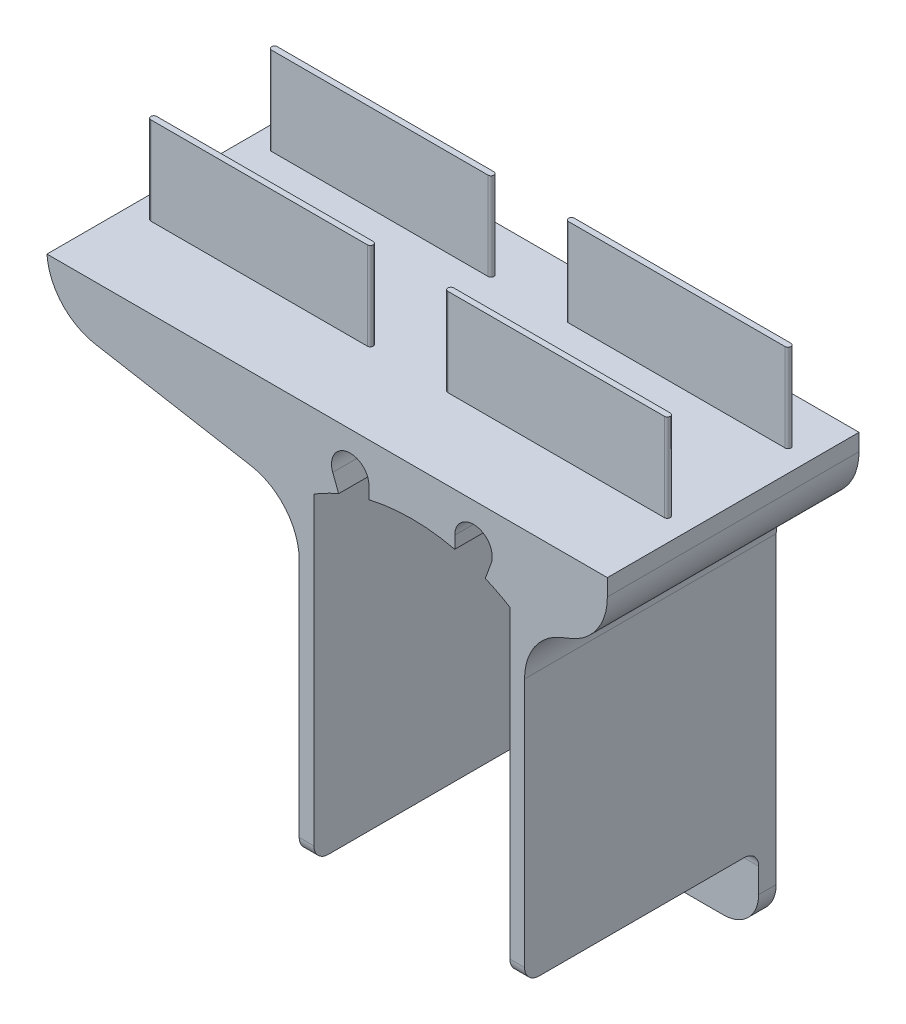
SolidWorks part; units mm, degrees
material "ABS"
ref_plane "Alzado" through (0, 0, 0) normal (0, 0, 1) x (1, 0, 0)
ref_plane "Planta" through (0, 0, 0) normal (0, 1, 0) x (1, 0, 0)
ref_plane "Vista lateral" through (0, 0, 0) normal (1, 0, 0) x (0, 0, -1)
sketch "Croquis4" plane through (0, 0, 0) normal (0, 0, 1) x (1, 0, 0)
  line L0 (-61.9253, -22.5138) -> (-61.9253, 45.4862)
  line L2 (-97.4253, -15.5138) -> (-97.4253, 38.4862) construction
  line L10 (-119.4893, 11.4862) -> (-75.3613, 11.4862) construction
  line L13 (-100.4253, -22.5138) -> (-100.4253, 45.4862)
  line L14 (-81.1753, 11.4862) -> (-81.1753, 55.3392) construction
  line L15 (-94.4253, 51.4862) -> (-67.9253, 51.4862)
  line L18 (-94.4253, -28.5138) -> (-67.9253, -28.5138)
  line L19 (-64.4253, -15.7955) -> (-64.4253, 38.7679)
  line L20 (-97.9253, -15.7955) -> (-97.9253, 38.7679)
  line L21 (-64.9253, -15.5138) -> (-64.9253, 38.4862) construction
  arc A0 (-61.9253, 45.4862) -> (-67.9253, 51.4862) centre (-67.9253, 45.4862) ccw
  arc A1 (-61.9253, -22.5138) -> (-67.9253, -28.5138) centre (-67.9253, -22.5138) cw
  arc A4 (-100.4253, -22.5138) -> (-94.4253, -28.5138) centre (-94.4253, -22.5138) ccw
  arc A5 (-97.4253, 38.4862) -> (-64.9253, 38.4862) centre (-81.1753, 11.3959) cw construction
  arc A6 (-97.4253, -15.5138) -> (-64.9253, -15.5138) centre (-81.1753, 11.5765) ccw construction
  arc A7 (-97.9253, 38.7679) -> (-64.4253, 38.7679) centre (-81.1753, 11.3959) cw
  circle A8 centre (-91.7053, -21.7638) radius 2.63 construction
  circle A9 centre (-70.6453, -21.7638) radius 2.63 construction
  circle A10 centre (-91.7053, 44.7362) radius 2.63 construction
  circle A11 centre (-70.6453, 44.7362) radius 2.63 construction
  arc A20 (-100.4253, 45.4862) -> (-94.4253, 51.4862) centre (-94.4253, 45.4862) cw
  arc A21 (-97.9253, -15.7955) -> (-64.4253, -15.7955) centre (-81.1753, 11.5765) ccw
  circle A22 centre (-91.7053, 44.7362) radius 1.6 construction
  circle A23 centre (-70.6453, 44.7362) radius 1.6 construction
  circle A24 centre (-70.6453, -21.7638) radius 1.6 construction
  circle A25 centre (-91.7053, -21.7638) radius 1.6 construction
  point P30 (-97.4253, 11.4862)
  point P31 (-81.1753, 42.9862)
  point P39 (-81.1753, 51.4862)
  point P43 (-61.9253, 11.4862)
  point P48 (-100.4253, 11.4862)
  dimension "D2" = 3.2
  dimension "D3" = 6
  dimension "D9" = 33.25
  dimension "D10" = 10.53
  dimension "D11" = 5.26
  dimension "D4" = 2.5
  dimension "D5" = 40
  dimension "D6" = 54
  dimension "D7" = 31.5
  dimension "D8" = 16.25
  dimension "D1" = 0.5
extrude "Saliente-Extruir1" add sketch "Croquis4" along normal blind 3
sketch "Croquis5" plane through (0, 0, 3) normal (0, 0, 1) x (1, 0, 0)
  line L8 (-64.4253, -15.7955) -> (-64.4253, 38.7679) construction
  line L9 (-97.9253, 38.7679) -> (-97.9253, -15.7955) construction
  line L10 (-64.4253, -15.7955) -> (-64.4253, 38.7679)
  line L11 (-97.9253, 38.7679) -> (-97.9253, -15.7955)
  line L12 (-61.9253, -15.7955) -> (-61.9253, 40.1348)
  line L13 (-100.4253, 40.1348) -> (-100.4253, -15.7955)
  line L14 (-100.4253, -15.7955) -> (-97.9253, -15.7955)
  line L15 (-64.4253, -15.7955) -> (-61.9253, -15.7955)
  arc A0 (-64.4253, 38.7679) -> (-97.9253, 38.7679) centre (-81.1753, 11.3959) ccw construction
  arc A6 (-64.4253, 38.7679) -> (-97.9253, 38.7679) centre (-81.1753, 11.3959) ccw
  arc A7 (-61.9253, 40.1348) -> (-100.4253, 40.1348) centre (-81.1753, 11.3959) ccw
  dimension "D1" = 2.5
extrude "Saliente-Extruir2" add sketch "Croquis5" along normal blind 40
ref_plane "Plano1" through (0, 51.4862, 0) normal (0, -1, 0) x (-1, 0, 0)
sketch "Croquis6" plane through (0, 51.4862, 0) normal (0, -1, 0) x (-1, 0, 0)
  line L8 (49.7713, -7.6345) -> (49.7713, -8.6345) construction
  line L9 (88.7713, -6.6345) -> (50.7713, -6.6345) construction
  line L10 (89.7713, -8.6345) -> (89.7713, -7.6345) construction
  line L11 (50.7713, -9.6345) -> (88.7713, -9.6345) construction
  line L12 (49.7713, -28.2595) -> (49.7713, -29.2595)
  line L13 (88.7713, -27.2595) -> (50.7713, -27.2595)
  line L14 (89.7713, -29.2595) -> (89.7713, -28.2595)
  line L15 (50.7713, -30.2595) -> (88.7713, -30.2595)
  line L16 (49.7713, -28.2595) -> (49.7713, -29.2595) construction
  line L17 (88.7713, -27.2595) -> (50.7713, -27.2595) construction
  line L18 (89.7713, -29.2595) -> (89.7713, -28.2595) construction
  line L19 (50.7713, -30.2595) -> (88.7713, -30.2595) construction
  line L20 (141.5232, -29.2595) -> (141.5232, -28.2595)
  line L21 (102.5232, -30.2595) -> (140.5232, -30.2595)
  line L22 (101.5232, -28.2595) -> (101.5232, -29.2595)
  line L23 (140.5232, -27.2595) -> (102.5232, -27.2595)
  line L24 (141.5232, -29.2595) -> (141.5232, -28.2595) construction
  line L25 (102.5232, -30.2595) -> (140.5232, -30.2595) construction
  line L26 (101.5232, -28.2595) -> (101.5232, -29.2595) construction
  line L27 (140.5232, -27.2595) -> (102.5232, -27.2595) construction
  line L28 (141.5232, -8.6345) -> (141.5232, -7.6345)
  line L29 (102.5232, -9.6345) -> (140.5232, -9.6345)
  line L30 (101.5232, -7.6345) -> (101.5232, -8.6345)
  line L31 (140.5232, -6.6345) -> (102.5232, -6.6345)
  line L32 (141.5232, -8.6345) -> (141.5232, -7.6345) construction
  line L33 (102.5232, -9.6345) -> (140.5232, -9.6345) construction
  line L34 (101.5232, -7.6345) -> (101.5232, -8.6345) construction
  line L35 (140.5232, -6.6345) -> (102.5232, -6.6345) construction
  arc A8 (50.7713, -6.6345) -> (49.7713, -7.6345) centre (50.7713, -7.6345) ccw construction
  arc A9 (89.7713, -7.6345) -> (88.7713, -6.6345) centre (88.7713, -7.6345) ccw construction
  arc A10 (88.7713, -9.6345) -> (89.7713, -8.6345) centre (88.7713, -8.6345) ccw construction
  arc A11 (49.7713, -8.6345) -> (50.7713, -9.6345) centre (50.7713, -8.6345) ccw construction
  arc A12 (50.7713, -27.2595) -> (49.7713, -28.2595) centre (50.7713, -28.2595) ccw
  arc A13 (89.7713, -28.2595) -> (88.7713, -27.2595) centre (88.7713, -28.2595) ccw
  arc A14 (88.7713, -30.2595) -> (89.7713, -29.2595) centre (88.7713, -29.2595) ccw
  arc A15 (49.7713, -29.2595) -> (50.7713, -30.2595) centre (50.7713, -29.2595) ccw
  arc A16 (50.7713, -27.2595) -> (49.7713, -28.2595) centre (50.7713, -28.2595) ccw construction
  arc A17 (89.7713, -28.2595) -> (88.7713, -27.2595) centre (88.7713, -28.2595) ccw construction
  arc A18 (88.7713, -30.2595) -> (89.7713, -29.2595) centre (88.7713, -29.2595) ccw construction
  arc A19 (49.7713, -29.2595) -> (50.7713, -30.2595) centre (50.7713, -29.2595) ccw construction
  arc A20 (140.5232, -30.2595) -> (141.5232, -29.2595) centre (140.5232, -29.2595) ccw
  arc A21 (101.5232, -29.2595) -> (102.5232, -30.2595) centre (102.5232, -29.2595) ccw
  arc A22 (102.5232, -27.2595) -> (101.5232, -28.2595) centre (102.5232, -28.2595) ccw
  arc A23 (141.5232, -28.2595) -> (140.5232, -27.2595) centre (140.5232, -28.2595) ccw
  arc A24 (140.5232, -30.2595) -> (141.5232, -29.2595) centre (140.5232, -29.2595) ccw construction
  arc A25 (101.5232, -29.2595) -> (102.5232, -30.2595) centre (102.5232, -29.2595) ccw construction
  arc A26 (102.5232, -27.2595) -> (101.5232, -28.2595) centre (102.5232, -28.2595) ccw construction
  arc A27 (141.5232, -28.2595) -> (140.5232, -27.2595) centre (140.5232, -28.2595) ccw construction
  arc A28 (140.5232, -9.6345) -> (141.5232, -8.6345) centre (140.5232, -8.6345) ccw
  arc A29 (101.5232, -8.6345) -> (102.5232, -9.6345) centre (102.5232, -8.6345) ccw
  arc A30 (102.5232, -6.6345) -> (101.5232, -7.6345) centre (102.5232, -7.6345) ccw
  arc A31 (141.5232, -7.6345) -> (140.5232, -6.6345) centre (140.5232, -7.6345) ccw
  arc A32 (140.5232, -9.6345) -> (141.5232, -8.6345) centre (140.5232, -8.6345) ccw construction
  arc A33 (101.5232, -8.6345) -> (102.5232, -9.6345) centre (102.5232, -8.6345) ccw construction
  arc A34 (102.5232, -6.6345) -> (101.5232, -7.6345) centre (102.5232, -7.6345) ccw construction
  arc A35 (141.5232, -7.6345) -> (140.5232, -6.6345) centre (140.5232, -7.6345) ccw construction
  dimension "D2" = 0
  dimension "D3" = 0
  dimension "D4" = 0
ref_plane "Plano2" through (0, 0, 30.2595) normal (0, 0, 1) x (1, 0, 0)
sketch "Croquis7" plane through (0, 0, 30.2595) normal (0, 0, 1) x (1, 0, 0)
  line L0 (-141.5232, 51.4862) -> (-140.5232, 51.4862) construction
  line L1 (-50.7713, 51.4862) -> (-49.7713, 51.4862) construction
  line L2 (-141.5232, 51.4862) -> (-140.5232, 51.4862) construction
  line L3 (-50.7713, 51.4862) -> (-49.7713, 51.4862) construction
  line L4 (-143.5232, 51.4862) -> (-143.5232, 43.7412)
  line L8 (-61.9253, -15.7955) -> (-61.9253, 40.1348) construction
  line L9 (-143.5232, 43.7412) -> (-100.4253, 36.1419)
  line L10 (-47.7713, 51.4862) -> (-47.7713, 41.8929)
  line L11 (-47.7713, 41.8929) -> (-61.9253, 36.1419)
  line L13 (-143.5232, 51.4862) -> (-47.7713, 51.4862)
  line L14 (-100.4253, 36.1419) -> (-100.4253, 40.1348)
  line L15 (-61.9253, 36.1419) -> (-61.9253, 40.1348)
  line L17 (-100.4253, 40.1348) -> (-100.4253, -15.7955) construction
  line L18 (-61.9253, -15.7955) -> (-61.9253, 40.1348) construction
  line L19 (-100.4253, 40.1348) -> (-100.4253, -15.7955) construction
  arc A2 (-61.9253, 40.1348) -> (-100.4253, 40.1348) centre (-81.1753, 11.3959) ccw construction
  arc A3 (-61.9253, 40.1348) -> (-100.4253, 40.1348) centre (-81.1753, 11.3959) ccw
  point P4 (-100.4253, 40.0084)
  point P6 (-61.9253, 39.9683)
  point P14 (-62.1753, 36.2003)
  point P20 (-100.4253, 38.0577)
  dimension "D1" = 2
  dimension "D2" = 2
  dimension "D3" = 100
extrude "Saliente-Extruir3" add sketch "Croquis7" against normal up to surface (30.2595 mm away) from surface up to face at (-81.1753, 11.4862, 0) starting at face at (-81.1753, 13.1492, 43)
fillet "Redondeo1" radius 10 4 edges at (-47.7713, 41.8929, 21.5) (-143.5232, 43.7412, 21.5) (-61.9253, 36.1419, 21.5) (-100.4253, 36.1419, 21.5)
sketch "Croquis8" plane through (0, 51.4862, 0) normal (0, 1, 0) x (1, 0, 0)
  line L0 (-88.7713, -7.6345) -> (-51.7713, -7.6345)
  line L1 (-88.7713, -8.6345) -> (-51.7713, -8.6345)
  line L4 (-88.7713, -27.2595) -> (-50.7713, -27.2595) construction
  line L5 (-49.7713, -28.2595) -> (-49.7713, -29.2595) construction
  line L6 (-50.7713, -30.2595) -> (-88.7713, -30.2595) construction
  line L7 (-89.7713, -29.2595) -> (-89.7713, -28.2595) construction
  line L8 (-140.5232, -27.2595) -> (-102.5232, -27.2595) construction
  line L9 (-101.5232, -28.2595) -> (-101.5232, -29.2595) construction
  line L10 (-102.5232, -30.2595) -> (-140.5232, -30.2595) construction
  line L11 (-141.5232, -29.2595) -> (-141.5232, -28.2595) construction
  line L12 (-140.5232, -6.6345) -> (-102.5232, -6.6345) construction
  line L13 (-101.5232, -7.6345) -> (-101.5232, -8.6345) construction
  line L14 (-102.5232, -9.6345) -> (-140.5232, -9.6345) construction
  line L15 (-141.5232, -8.6345) -> (-141.5232, -7.6345) construction
  line L16 (-88.7713, -6.6345) -> (-50.7713, -6.6345) construction
  line L17 (-49.7713, -7.6345) -> (-49.7713, -8.6345) construction
  line L18 (-50.7713, -9.6345) -> (-88.7713, -9.6345) construction
  line L19 (-89.7713, -8.6345) -> (-89.7713, -7.6345) construction
  line L20 (-88.7713, -27.2595) -> (-50.7713, -27.2595) construction
  line L21 (-49.7713, -28.2595) -> (-49.7713, -29.2595) construction
  line L22 (-50.7713, -30.2595) -> (-88.7713, -30.2595) construction
  line L23 (-89.7713, -29.2595) -> (-89.7713, -28.2595) construction
  line L24 (-140.5232, -27.2595) -> (-102.5232, -27.2595) construction
  line L25 (-101.5232, -28.2595) -> (-101.5232, -29.2595) construction
  line L26 (-102.5232, -30.2595) -> (-140.5232, -30.2595) construction
  line L27 (-141.5232, -29.2595) -> (-141.5232, -28.2595) construction
  line L28 (-140.5232, -6.6345) -> (-102.5232, -6.6345) construction
  line L29 (-101.5232, -7.6345) -> (-101.5232, -8.6345) construction
  line L30 (-102.5232, -9.6345) -> (-140.5232, -9.6345) construction
  line L31 (-141.5232, -8.6345) -> (-141.5232, -7.6345) construction
  line L52 (-95.6473, 0) -> (-95.6473, -43) construction
  line L58 (-143.5232, -43) -> (-47.7713, -43) construction
  line L63 (-88.7713, -28.2595) -> (-51.7713, -28.2595)
  line L64 (-88.7713, -29.2595) -> (-51.7713, -29.2595)
  line L66 (-102.5232, -8.6345) -> (-139.5232, -8.6345)
  line L67 (-102.5232, -7.6345) -> (-139.5232, -7.6345)
  line L71 (-102.5232, -28.2595) -> (-139.5232, -28.2595)
  line L72 (-102.5232, -29.2595) -> (-139.5232, -29.2595)
  arc A0 (-88.7713, -8.6345) -> (-88.7713, -7.6345) centre (-88.7713, -8.1345) cw
  arc A1 (-51.7713, -7.6345) -> (-51.7713, -8.6345) centre (-51.7713, -8.1345) cw
  arc A4 (-49.7713, -28.2595) -> (-50.7713, -27.2595) centre (-50.7713, -28.2595) ccw construction
  arc A5 (-50.7713, -30.2595) -> (-49.7713, -29.2595) centre (-50.7713, -29.2595) ccw construction
  arc A6 (-89.7713, -29.2595) -> (-88.7713, -30.2595) centre (-88.7713, -29.2595) ccw construction
  arc A7 (-88.7713, -27.2595) -> (-89.7713, -28.2595) centre (-88.7713, -28.2595) ccw construction
  arc A8 (-101.5232, -28.2595) -> (-102.5232, -27.2595) centre (-102.5232, -28.2595) ccw construction
  arc A9 (-102.5232, -30.2595) -> (-101.5232, -29.2595) centre (-102.5232, -29.2595) ccw construction
  arc A10 (-141.5232, -29.2595) -> (-140.5232, -30.2595) centre (-140.5232, -29.2595) ccw construction
  arc A11 (-140.5232, -27.2595) -> (-141.5232, -28.2595) centre (-140.5232, -28.2595) ccw construction
  arc A12 (-101.5232, -7.6345) -> (-102.5232, -6.6345) centre (-102.5232, -7.6345) ccw construction
  arc A13 (-102.5232, -9.6345) -> (-101.5232, -8.6345) centre (-102.5232, -8.6345) ccw construction
  arc A14 (-141.5232, -8.6345) -> (-140.5232, -9.6345) centre (-140.5232, -8.6345) ccw construction
  arc A15 (-140.5232, -6.6345) -> (-141.5232, -7.6345) centre (-140.5232, -7.6345) ccw construction
  arc A16 (-49.7713, -7.6345) -> (-50.7713, -6.6345) centre (-50.7713, -7.6345) ccw construction
  arc A17 (-50.7713, -9.6345) -> (-49.7713, -8.6345) centre (-50.7713, -8.6345) ccw construction
  arc A18 (-89.7713, -8.6345) -> (-88.7713, -9.6345) centre (-88.7713, -8.6345) ccw construction
  arc A19 (-88.7713, -6.6345) -> (-89.7713, -7.6345) centre (-88.7713, -7.6345) ccw construction
  arc A20 (-49.7713, -28.2595) -> (-50.7713, -27.2595) centre (-50.7713, -28.2595) ccw construction
  arc A21 (-50.7713, -30.2595) -> (-49.7713, -29.2595) centre (-50.7713, -29.2595) ccw construction
  arc A22 (-89.7713, -29.2595) -> (-88.7713, -30.2595) centre (-88.7713, -29.2595) ccw construction
  arc A23 (-88.7713, -27.2595) -> (-89.7713, -28.2595) centre (-88.7713, -28.2595) ccw construction
  arc A24 (-101.5232, -28.2595) -> (-102.5232, -27.2595) centre (-102.5232, -28.2595) ccw construction
  arc A25 (-102.5232, -30.2595) -> (-101.5232, -29.2595) centre (-102.5232, -29.2595) ccw construction
  arc A26 (-141.5232, -29.2595) -> (-140.5232, -30.2595) centre (-140.5232, -29.2595) ccw construction
  arc A27 (-140.5232, -27.2595) -> (-141.5232, -28.2595) centre (-140.5232, -28.2595) ccw construction
  arc A28 (-101.5232, -7.6345) -> (-102.5232, -6.6345) centre (-102.5232, -7.6345) ccw construction
  arc A29 (-102.5232, -9.6345) -> (-101.5232, -8.6345) centre (-102.5232, -8.6345) ccw construction
  arc A30 (-141.5232, -8.6345) -> (-140.5232, -9.6345) centre (-140.5232, -8.6345) ccw construction
  arc A31 (-140.5232, -6.6345) -> (-141.5232, -7.6345) centre (-140.5232, -7.6345) ccw construction
  arc A32 (-102.5232, -8.6345) -> (-102.5232, -7.6345) centre (-102.5232, -8.1345) ccw
  arc A33 (-139.5232, -7.6345) -> (-139.5232, -8.6345) centre (-139.5232, -8.1345) ccw
  arc A34 (-102.5232, -28.2595) -> (-102.5232, -29.2595) centre (-102.5232, -28.7595) cw
  arc A35 (-139.5232, -29.2595) -> (-139.5232, -28.2595) centre (-139.5232, -28.7595) cw
  arc A36 (-51.7713, -29.2595) -> (-51.7713, -28.2595) centre (-51.7713, -28.7595) ccw
  arc A37 (-88.7713, -28.2595) -> (-88.7713, -29.2595) centre (-88.7713, -28.7595) ccw
  dimension "D1" = 37
extrude "Saliente-Extruir4" add sketch "Croquis8" along normal blind 15
sketch "Croquis12" plane through (0, 0, 0) normal (0, 0, -1) x (-1, 0, 0)
  circle A9 centre (91.7053, 44.7362) radius 1.6 construction
  circle A10 centre (70.6453, 44.7362) radius 1.6 construction
  circle A11 centre (91.7053, -21.7638) radius 1.6 construction
  circle A12 centre (70.6453, -21.7638) radius 1.6 construction
  circle A13 centre (91.7053, 44.7362) radius 1.6
  circle A14 centre (70.6453, 44.7362) radius 1.6
  circle A15 centre (91.7053, -21.7638) radius 1.6
  circle A16 centre (70.6453, -21.7638) radius 1.6
extrude "Cortar-Extruir2" cut sketch "Croquis12" against normal blind 3
sketch "Croquis13" plane through (0, 0, 0) normal (0, 0, -1) x (-1, 0, 0)
  circle A4 centre (70.6453, 44.7362) radius 3.2
  circle A5 centre (91.7053, 44.7362) radius 3.2
  circle A6 centre (91.7053, 44.7362) radius 1.6 construction
  circle A7 centre (70.6453, 44.7362) radius 1.6 construction
  circle A8 centre (91.7053, 44.7362) radius 1.6 construction
  circle A9 centre (70.6453, 44.7362) radius 1.6 construction
  dimension "D1" = 6.4
extrude "Cortar-Extruir3" cut sketch "Croquis13" against normal through all from offset 3 offset against normal yes
fillet "Redondeo2" radius 2.5 4 edges at (-99.1753, -15.7955, 43) (-63.1753, -15.7955, 43) (-99.1753, -15.7955, 3) (-63.1753, -15.7955, 3)
sketch "Croquis14" plane through (0, 0, 43) normal (0, 0, 1) x (1, 0, 0)
  line L0 (-94.6961, 43.5981) -> (-92.2758, 37.2381)
  line L1 (-92.2758, 37.2381) -> (-88.5053, 37.2381)
  line L2 (-88.5053, 37.2381) -> (-88.5053, 44.7362)
  line L3 (-73.8453, 44.7362) -> (-73.8453, 37.2381)
  line L5 (-69.9862, 37.2381) -> (-67.6409, 43.6346)
  line L6 (-73.8453, 37.2381) -> (-69.9862, 37.2381)
  circle A0 centre (-70.6453, 44.7362) radius 3.2 construction
  circle A1 centre (-91.7053, 44.7362) radius 3.2 construction
  arc A2 (-67.6409, 43.6346) -> (-73.8453, 44.7362) centre (-70.6453, 44.7362) ccw
  arc A3 (-88.5053, 44.7362) -> (-94.6961, 43.5981) centre (-91.7053, 44.7362) ccw
  arc A5 (-94.326, 40.6679) -> (-102.4971, 35.3786) centre (-81.1753, 11.3959) ccw construction
  arc A6 (-92.1179, 41.5629) -> (-97.9253, 38.7679) centre (-81.1753, 11.3959) ccw construction
extrude "Cortar-Extruir4" cut sketch "Croquis14" against normal up to surface (40 mm away) up to face at (-72.2453, 44.7362, 3)
